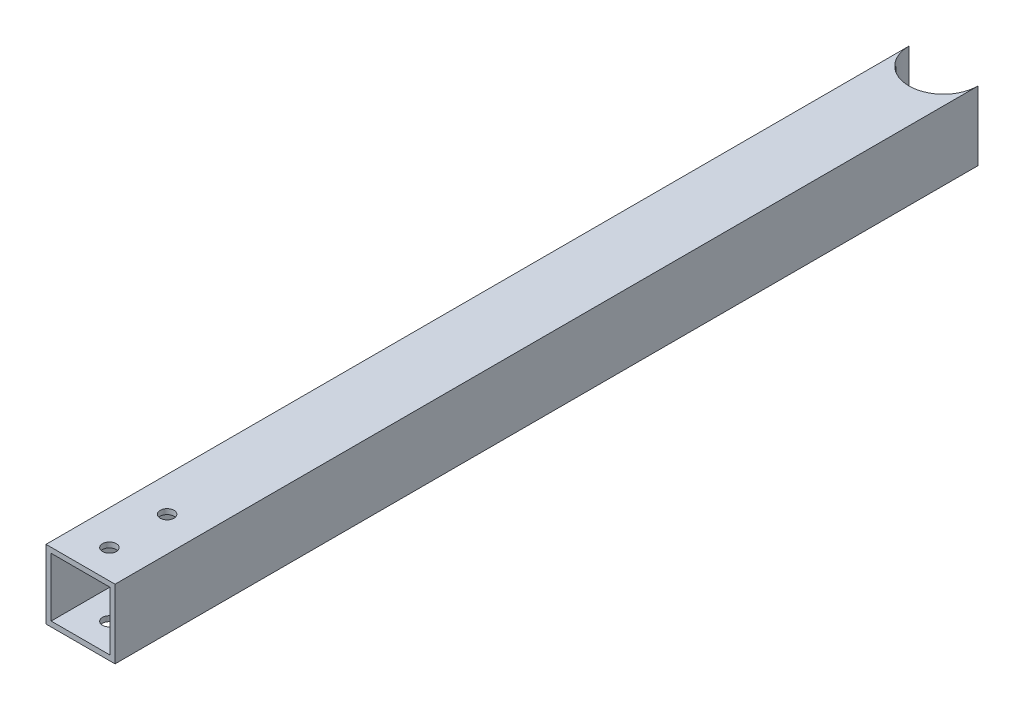
SolidWorks part; units mm, degrees
ref_plane "Front Plane" through (0, 0, 0) normal (0, 0, 1) x (1, 0, 0)
ref_plane "Top Plane" through (0, 0, 0) normal (0, 1, 0) x (1, 0, 0)
ref_plane "Right Plane" through (0, 0, 0) normal (1, 0, 0) x (0, 0, -1)
sketch "Sketch1" plane through (0, 0, 0) normal (0, 0, 1) x (1, 0, 0)
  line L0 (3, 3) -> (3, 37)
  line L1 (0, 0) -> (40, 0)
  line L2 (0, 0) -> (0, 40)
  line L3 (0, 40) -> (40, 40)
  line L4 (40, 0) -> (40, 40)
  line L5 (3, 37) -> (37, 37)
  line L6 (37, 3) -> (37, 37)
  line L7 (3, 3) -> (37, 3)
  dimension "D1" = 40
  dimension "D2" = 40
  dimension "D3" = 3
extrude "Boss-Extrude1" add sketch "Sketch1" along normal blind 500
sketch "Sketch2" plane through (0, 40, 0) normal (0, 1, 0) x (1, 0, 0)
  line L0 (30, -500) -> (30, -433.0924)
  line L1 (30, -433.0924) -> (10, -433.0924)
  line L2 (10, -433.0924) -> (10, -500)
  line L3 (10, -500) -> (30, -500)
  line L4 (40, 0) -> (0, 0) construction
  circle A0 centre (20, -483.2731) radius 4
  circle A1 centre (20, -449.8193) radius 4
  circle A2 centre (20, 0) radius 20
extrude "Cut-Extrude1" cut sketch "Sketch2" against normal blind 600 contours A1 | A0 | A2 region at (20, 40, 483.2731) region at (20, 40, 449.8193)
